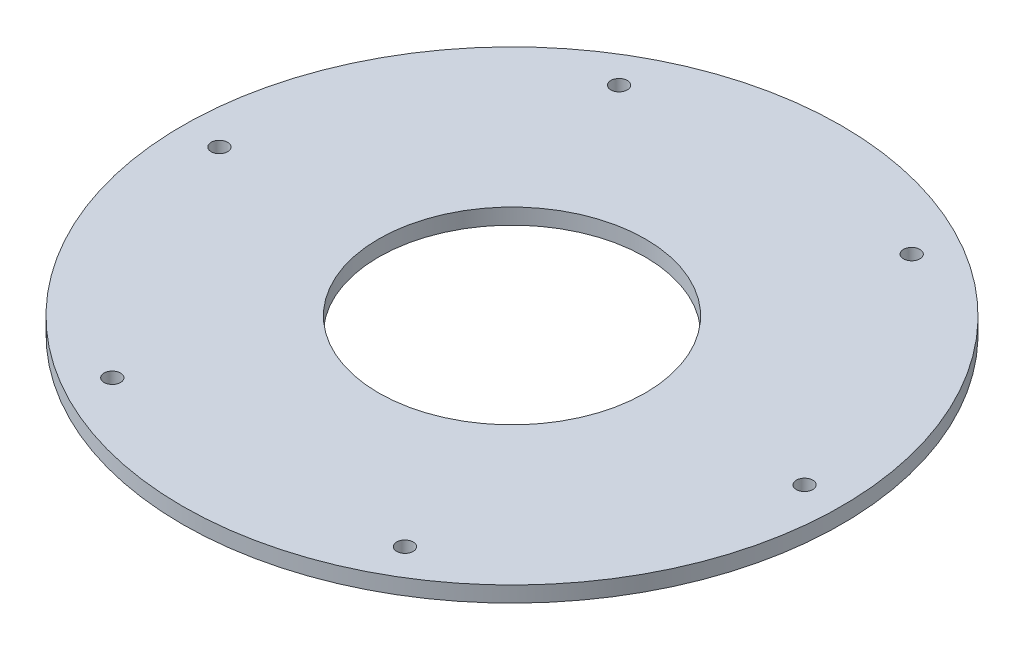
SolidWorks part; units mm, degrees
material "1060 Alloy"
ref_plane "Front Plane" through (0, 0, 0) normal (0, 0, 1) x (1, 0, 0)
ref_plane "Top Plane" through (0, 0, 0) normal (0, 1, 0) x (1, 0, 0)
ref_plane "Right Plane" through (0, 0, 0) normal (1, 0, 0) x (0, 0, -1)
sketch "Sketch2" plane through (0, 0, 0) normal (0, 1, 0) x (1, 0, 0)
  line L0 (-37.2875, 0) -> (0, 0) construction
  circle A0 centre (0, 0) radius 42
  circle A1 centre (0, 0) radius 37.2875 construction
  circle A2 centre (-37.2875, 0) radius 1.05
  circle A3 centre (-18.6438, 32.2919) radius 1.05
  circle A4 centre (18.6438, 32.2919) radius 1.05
  circle A5 centre (37.2875, 0) radius 1.05
  circle A6 centre (18.6438, -32.2919) radius 1.05
  circle A7 centre (-18.6437, -32.2919) radius 1.05
  circle A8 centre (0, 0) radius 17
  point P6 (0, 0)
  point P18 (0, 0)
  dimension "D1" = 2.1
  dimension "D3" = 74.575
  dimension "D4" = 84
  dimension "D5" = 34
  dimension "D2" = 6
extrude "Boss-Extrude1" add sketch "Sketch2" along normal blind 2
equation "\"D5@Sketch2\" = \"Rotor_ID\""
equation "\"Stator_OD\"= 68'No Tolerance given"
equation "\"A\"=18.34 'taken off spec sheet for 06808 (A)"
equation "\"Rotor_ID\"= 34'No Tolerance Given"
equation "\"back_bearing_Thickness\"= 8'randomish, thinnest off mcmaster"
equation "\"back_bearing_OD\"= 25'currently non-sense"
equation "\"Stator_Gap\"= 0.0375'+- 0.0125 (From 1.3.3.1 Kollmorgen manual)"
equation "\"Back_mount_hole\"= 1.75'To be tapped to M2 (USE LOCKTITE)"
equation "\"facePlate_Mount_Hole\"= 5.75'To be tapped to M6"
equation "\"back_bearing_ID\"= 15'Random number"
equation "\"final_shaftD\"= 8'NEMA 23 shaft diameter. Should fit with harmonic?"
equation "\"final_shaftL\"= 50'random length. Idk"
equation "\"back_bearing_IDOD\"= 20'Random number, OD of the inner bearing ring"
equation "\"rotor_shaftD\"= \"Rotor_ID\" - (0.0185)*2'+-0.0065 (from manual)"
equation "\"D4@Sketch2\"=\"Stator_OD\"+16"
equation "\"D3@Sketch2\"=\"Stator_OD\"+\"Stator_Gap\"*2+6.5"
equation "\"front_bearing_ID\"= 12'random"
equation "\"front_bearing_OD\"= 20'random"
equation "\"front_bearing_IDOD\"= 14'random"
equation "\"front_bearing_Thickness\"= 5'randomish, thinnest off mcmaster"
equation "\"rotor_thickness\"= 2.4'measured off CAD"
equation "\"rotor_height\"= 14.76'+-0.08 taken off spec sheet for 06808 (C)"
